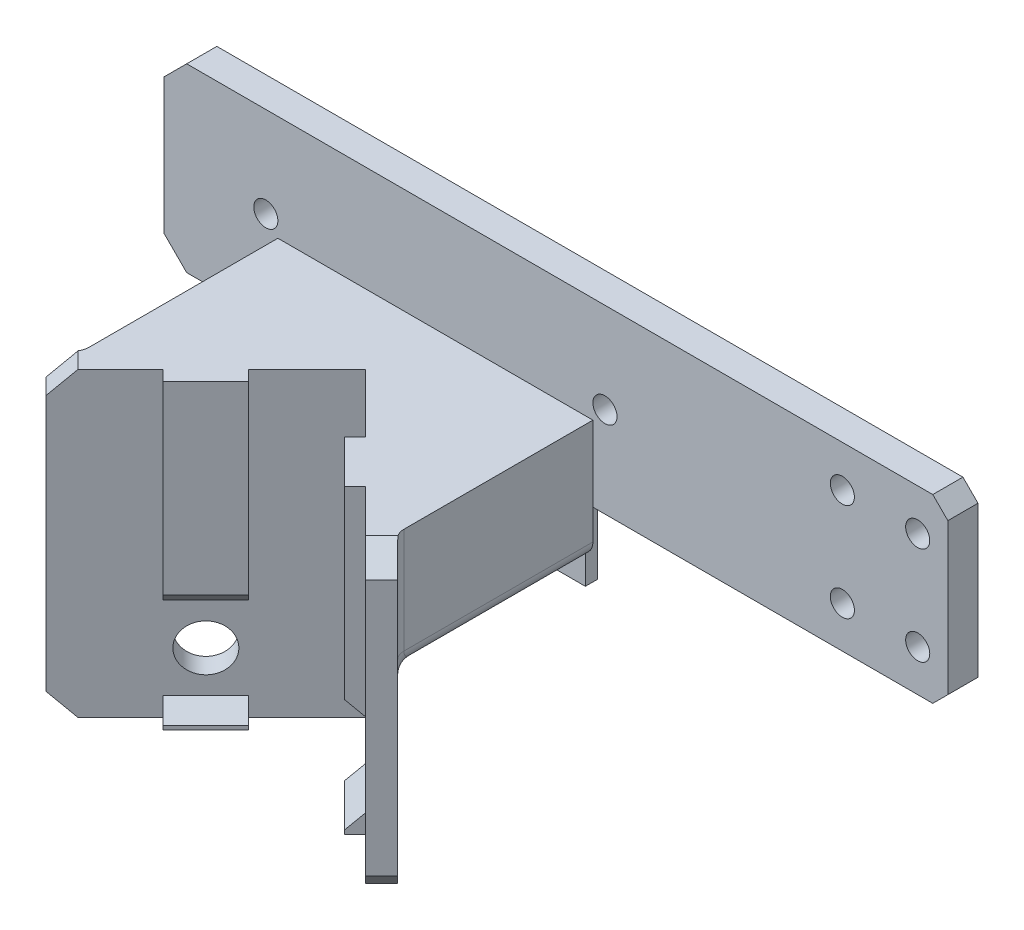
SolidWorks part; units mm, degrees
ref_plane "Alzado" through (0, 0, 0) normal (0, 0, 1) x (1, 0, 0)
ref_plane "Planta" through (0, 0, 0) normal (0, 1, 0) x (1, 0, 0)
ref_plane "Vista lateral" through (0, 0, 0) normal (1, 0, 0) x (0, 0, -1)
sketch "Croquis1" plane through (0, 0, 0) normal (0, 0, 1) x (1, 0, 0)
  line L0 (0, 0) -> (0, 18835.1574) construction
  line L1 (0, 0) -> (-18835.1574, 0) construction
  line L2 (12.5, -12) -> (36, -12)
  line L3 (-36, -12) -> (36, -12) construction
  line L4 (-36, -12) -> (-36, 12)
  line L5 (-36, 12) -> (36, 12)
  line L6 (36, -12) -> (36, 12)
  line L7 (-36, -12) -> (36, 12) construction
  line L8 (-36, 12) -> (36, -12) construction
  line L9 (-17.5, 6) -> (17.5, 6) construction
  line L10 (-17.5, 6) -> (-17.5, -6) construction
  line L11 (-17.5, -6) -> (17.5, -6) construction
  line L12 (17.5, 6) -> (17.5, -6) construction
  line L13 (-17.5, 6) -> (17.5, -6) construction
  line L14 (-17.5, -6) -> (17.5, 6) construction
  line L15 (-12.5, -24) -> (12.5, -24)
  line L16 (-12.5, -24) -> (-12.5, -12)
  line L17 (-12.5, -12) -> (12.5, -12) construction
  line L18 (12.5, -24) -> (12.5, -12)
  line L19 (-12.5, -24) -> (12.5, -12) construction
  line L20 (-12.5, -12) -> (12.5, -24) construction
  line L21 (-36, -12) -> (-12.5, -12)
  circle A0 centre (-22.5, 0) radius 1.6
  circle A1 centre (22.5, 0) radius 1.6
  point P7 (0, 0)
  point P12 (0, -18)
  point P16 (0, 0)
  dimension "D1" = 3.2
  dimension "D2" = 45
  dimension "D3" = 24
  dimension "D4" = 13.5
  dimension "D5" = 35
  dimension "D6" = 12
  dimension "D7" = 12
  dimension "D8" = 25
extrude "Saliente-Extruir1" add sketch "Croquis1" along normal blind 4
sketch "Croquis3" plane through (0, 0, 0) normal (0, 0, -1) x (-1, 0, 0)
  line L0 (0, 0) -> (-50000, 0) construction
  line L1 (-66, 12) -> (-36, 12)
  line L2 (-66, -12) -> (-36, -12)
  line L3 (-36, -12) -> (-36, 12)
  line L4 (-36, -12) -> (-36, 12) construction
  line L5 (-66, 12) -> (-68, 10)
  line L6 (-68, 10) -> (-68, -10)
  line L7 (-66, -12) -> (-68, -10)
  arc A0 (-66, 12) -> (-66, -12) centre (-66, 0) ccw construction
  circle A1 centre (-54, 6.5) radius 1.6
  circle A2 centre (-64, 6.5) radius 1.6
  circle A3 centre (-54, -6.5) radius 1.6
  circle A4 centre (-64, -6.5) radius 1.6
  point P22 (-68, 0)
  dimension "D1" = 30
  dimension "D2" = 3.2
  dimension "D5" = 28
  dimension "D3" = 13
  dimension "D4" = 18
  dimension "D6" = 32
  dimension "D7" = 2
extrude "Saliente-Extruir3" add sketch "Croquis3" against normal blind 4
ref_plane "Plano1" through (0, -12, 0) normal (0, -1, 0) x (1, 0, 0)
sketch "Croquis5" plane through (0, -12, 0.2843) normal (0, 1, 0) x (1, 0, 0)
  line L0 (0, 0) -> (0, 50000) construction
  line L2 (-21.2132, -34.1716) -> (0, -12.9584) construction
  line L5 (-13.435, -26.3934) -> (-21.2132, -34.1716)
  line L11 (-10, -3.7157) -> (49990, -3.7157) construction
  line L12 (0, -8.7157) -> (23.3345, -32.0503)
  line L13 (23.3345, -32.0503) -> (21.2132, -34.1716)
  line L14 (21.2132, -34.1716) -> (0, -12.9584) construction
  line L38 (9.2023, -24.9692) -> (35364.5414, 35330.3698) construction
  line L39 (0, -12.9584) -> (-7.7782, -20.7365)
  line L40 (7.7782, -20.7365) -> (6.364, -22.1508)
  line L41 (6.364, -22.1508) -> (12.0208, -27.8076)
  line L42 (12.0208, -27.8076) -> (13.435, -26.3934)
  line L43 (0, -12.9584) -> (7.7782, -20.7365)
  line L44 (13.435, -26.3934) -> (21.2132, -34.1716)
  line L45 (-12.0208, -27.8076) -> (-13.435, -26.3934)
  line L46 (-6.364, -22.1508) -> (-12.0208, -27.8076)
  line L47 (-7.7782, -20.7365) -> (-6.364, -22.1508)
  line L48 (-23.3345, -32.0503) -> (-21.2132, -34.1716)
  line L49 (0, -8.7157) -> (-23.3345, -32.0503)
  point P13 (10.6066, -23.565)
  point P19 (9.1924, -24.9792)
  dimension "D1" = 45
  dimension "D2" = 30
  dimension "D3" = 3
  dimension "D4" = 2
  dimension "D5" = 8
  dimension "D6" = 5
extrude "Saliente-Extruir4" add sketch "Croquis5" against normal blind 30 and the other way blind 10
sketch "Croquis24" plane through (0, -2, 0) normal (0, 1, 0) x (1, 0, 0)
  line L0 (-20.9, -4) -> (-20.9, -29.9)
  line L1 (0, -9) -> (-23.3345, -32.3345) construction
  line L2 (-20.9, -29.9) -> (0, -9)
  line L3 (0, -9) -> (20.9, -29.9)
  line L4 (23.3345, -32.3345) -> (0, -9) construction
  line L5 (20.9, -29.9) -> (20.9, -4)
  line L6 (20.9, -4) -> (-20.9, -4)
extrude "Saliente-Extruir7" add sketch "Croquis24" against normal blind 16
sketch "Croquis13" plane through (-8.0355, 0, 8.0355) normal (-0.7071, 0, 0.7071) x (0.665, 0.3399, 0.665)
  line L0 (10.5188, -42.5729) -> (6527.199, 17986.9124) construction
  line L1 (4.8746, -46.4212) -> (12.3982, -49.1406) construction
  line L3 (18.4715, -8.8031) -> (25.9951, -11.5225) construction
  circle A0 centre (11.3558, -40.2573) radius 3.1
  point P4 (8.6364, -47.7809)
  point P9 (22.2333, -10.1628)
  dimension "D1" = 6.2
  dimension "D2" = 8
extrude "Cortar-Extruir8" cut sketch "Croquis13" against normal up to next
sketch "Croquis14" plane through (-8.0355, 0, 8.0355) normal (-0.7071, 0, 0.7071) x (0.665, 0.3399, 0.665)
  line L0 (6.0643, -43.1296) -> (13.588, -45.849)
  line L1 (18.4715, -8.8031) -> (4.8746, -46.4212) construction
  line L2 (25.9951, -11.5225) -> (12.3982, -49.1406) construction
  line L3 (13.588, -45.849) -> (16.6473, -37.3849)
  line L4 (25.9951, -11.5225) -> (12.3982, -49.1406) construction
  line L5 (16.6473, -37.3849) -> (9.1236, -34.6655)
  line L6 (18.4715, -8.8031) -> (4.8746, -46.4212) construction
  line L7 (9.1236, -34.6655) -> (6.0643, -43.1296)
  line L8 (7.594, -38.8976) -> (15.1176, -41.617) construction
  point P16 (11.3558, -40.2573)
  dimension "D1" = 9
extrude "Cortar-Extruir9" cut sketch "Croquis14" against normal up to surface (2 mm away) up to face at (17.3241, -22, 30.5668)
sketch "Croquis15" plane through (3.0443, 2.5513, 13.0267) normal (0.7071, 0, 0.7071) x (0.6817, 0.2654, -0.6817)
  line L0 (-8.4296, -38.5546) -> (28417.7576, -12556.7321) construction
  line L2 (-21.6754, -13.5352) -> (-7681.2772, -27836.3049) construction
  line L3 (-21.7492, 1.2669) -> (-14.0361, -0.8565) construction
  line L4 (-32.3662, -37.2983) -> (-24.6531, -39.4217) construction
  circle A0 centre (-26.3863, -30.647) radius 3.1
  point P8 (-17.8927, 0.2052)
  point P11 (-28.5097, -38.36)
  dimension "D1" = 6.2
  dimension "D2" = 8
extrude "Cortar-Extruir10" cut sketch "Croquis15" against normal up to next
sketch "Croquis17" plane through (3.0443, 2.5513, 13.0267) normal (0.7071, 0, 0.7071) x (0.6817, 0.2654, -0.6817)
  line L0 (-31.4372, -33.9239) -> (-23.7241, -36.0473)
  line L3 (-23.7241, -36.0473) -> (-21.3353, -27.3701)
  line L5 (-21.3353, -27.3701) -> (-29.0484, -25.2467)
  line L7 (-29.0484, -25.2467) -> (-31.4372, -33.9239)
  line L8 (-30.2428, -29.5853) -> (-22.5297, -31.7087) construction
  line L10 (-14.0361, -0.8565) -> (-24.6531, -39.4217) construction
  line L11 (-21.7492, 1.2669) -> (-32.3662, -37.2983) construction
  line L12 (-21.7492, 1.2669) -> (-32.3662, -37.2983) construction
  point P2 (-13.1428, -24.272)
  point P3 (-26.3863, -30.647)
  point P11 (-26.3863, -30.647)
  point P16 (-6.8436, -36.0271)
  dimension "D1" = 9
extrude "Cortar-Extruir11" cut sketch "Croquis17" against normal up to surface (2 mm away) up to face at (-17.3241, -22, 30.5668)
chamfer "Chaflán1" distance 3 angle 45 10 edges at (22.2739, -2, 33.3952) (22.2739, -42, 33.3952) (-22.2739, -2, 33.3952) (-22.2739, -42, 33.3952) (-36, -12, 2) (-36, 12, 2) (9.1924, -29.5, 25.2635) (-9.1924, -29.5, 25.2635) (-9.1924, -38.5, 25.2635) (9.1924, -38.5, 25.2635)
fillet "Redondeo2" [suppressed] radius 5
sketch "Croquis20" plane through (0, 0, 0) normal (0, 0, -1) x (-1, 0, 0)
  line L0 (0, 0) -> (0, 50000) construction
  line L1 (-17.5, -12) -> (49982.5, -12) construction
  line L2 (-42.5097, -24) -> (49957.4903, -24) construction
  line L4 (-17.5, -24) -> (17.5, -24)
  line L5 (-17.5, -24) -> (-17.5, -12)
  line L6 (-17.5, -12) -> (17.5, -12)
  line L7 (17.5, -24) -> (17.5, -12)
  line L8 (-17.5, -24) -> (17.5, -12) construction
  line L9 (-17.5, -12) -> (17.5, -24) construction
  point P8 (0, -18)
  dimension "D1" = 12
extrude "Saliente-Extruir6" add sketch "Croquis20" against normal blind 1.6
sketch "Croquis23" plane through (0, -42, 0) normal (0, -1, 0) x (1, 0, 0)
  line L0 (21.2132, 30.2132) -> (0, 9) construction
  line L1 (14.92, 25.3342) -> (19.0919, 29.5061)
  line L2 (23.3345, 32.3345) -> (21.2132, 30.2132) construction
  line L3 (17.6777, 30.9203) -> (13.5057, 26.7484)
  line L4 (13.5057, 22.5057) -> (14.92, 23.92)
  line L5 (20.5061, 29.5061) -> (21.9203, 30.9203)
  line L6 (13.435, 26.6777) -> (19.0919, 32.3345) construction
  line L7 (21.2132, 34.4558) -> (23.3345, 32.3345) construction
  arc A0 (14.92, 23.92) -> (14.92, 25.3342) centre (15.6271, 24.6271) cw
  arc A1 (19.0919, 29.5061) -> (20.5061, 29.5061) centre (19.799, 28.799) cw
  arc A2 (21.9203, 30.9203) -> (17.6777, 30.9203) centre (19.799, 28.799) ccw
  arc A3 (13.5057, 26.7484) -> (13.5057, 22.5057) centre (15.6271, 24.6271) ccw
  dimension "D1" = 2
  dimension "D3" = 2
  dimension "D2" = 2
extrude "Cortar-Extruir13" cut sketch "Croquis23" against normal blind 4 from offset 16 offset against normal yes
fillet "Redondeo3" radius 2 7 edges at (-10.45, -18, 19.45) (10.45, -18, 19.45) (20.9, -10, 29.9) (-20.9, -10, 29.9) (0, -24, 4) (20.9, -18, 16.95) (-20.9, -18, 16.95)
